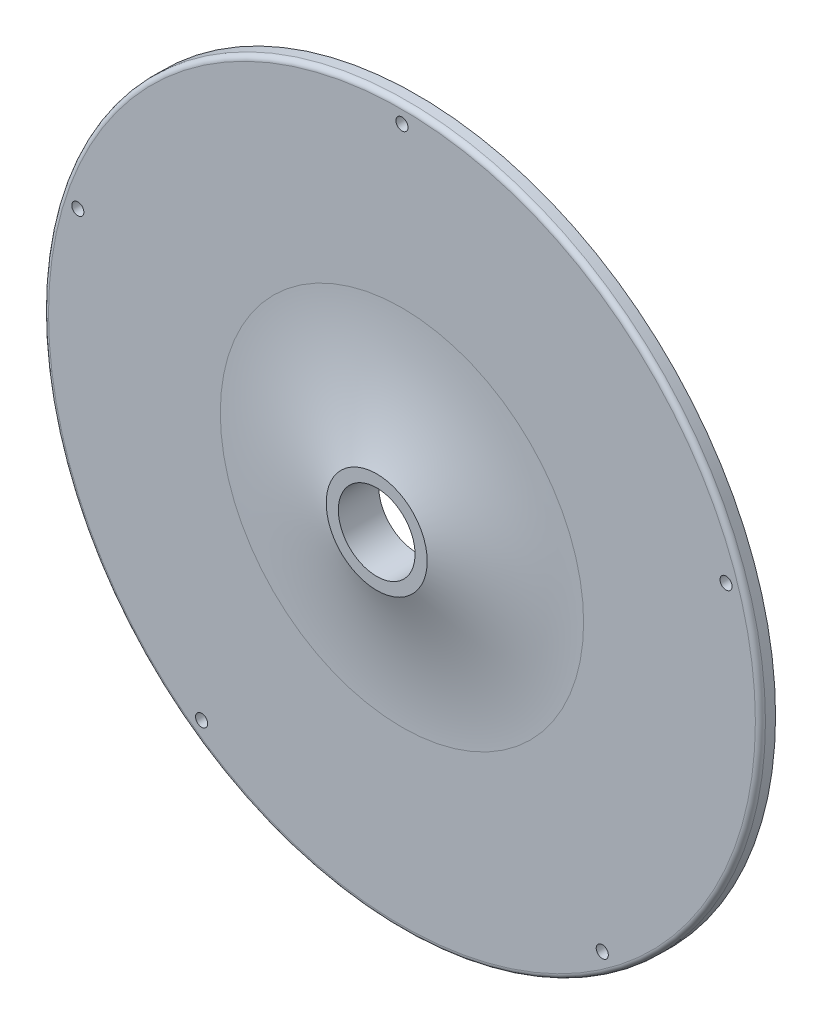
SolidWorks part; units mm, degrees
ref_plane "Front Plane" through (0, 0, 0) normal (0, 0, 1) x (1, 0, 0)
ref_plane "Top Plane" through (0, 0, 0) normal (0, 1, 0) x (1, 0, 0)
ref_plane "Right Plane" through (0, 0, 0) normal (1, 0, 0) x (0, 0, -1)
ref_axis "X AXIS" through (-88.99, 0, 0) along (1, 0, 0)
ref_axis "Y AXIS" through (0, 55, 0) along (0, -1, 0)
ref_axis "Z AXIS" through (0, 0, -88.99) along (0, 0, 1)
sketch "Sketch2" plane through (0, 0, 0) normal (0, 0, 1) x (1, 0, 0)
  circle A0 centre (0, 0) radius 81.28
  dimension "D1" = 162.56
extrude "Boss-Extrude1" add sketch "Sketch2" against normal blind 1.27
sketch "Sketch3" plane through (0, 0, 0) normal (0, 0, 1) x (1, 0, 0)
  circle A0 centre (0, 0) radius 90.17
  dimension "D1" = 180.34
extrude "Boss-Extrude2" add sketch "Sketch3" along normal blind 3.81
sketch "Sketch4" plane through (0, 0, 0) normal (0, 0, 1) x (1, 0, 0)
  line L0 (0, 88.9) -> (0, 82.55) construction
  circle A0 centre (0, 0) radius 82.55 construction
  circle A1 centre (0, 0) radius 88.9 construction
  circle A2 centre (0, 85.725) radius 1.524
  dimension "D1" = 165.1
  dimension "D2" = 177.8
  dimension "D3" = 3.048
extrude "Cut-Extrude2" cut sketch "Sketch4" along normal through all
pattern_circular "CirPattern1" count 5 over 360 about axis through (0, 0, 3.81) along (0, 0, 1) of "Cut-Extrude2"
sketch "Sketch14" plane through (0, 0, 3.81) normal (0, 0, 1) x (1, 0, 0)
  circle A0 centre (0, 0) radius 6.477
  circle A1 centre (0, 0) radius 12.7
  dimension "D1" = 12.954
  dimension "D2" = 25.4
extrude "Boss-Extrude3" add sketch "Sketch14" along normal blind 6.35 contours A1 A0 region at (-12.3408, 0, 3.81)
sketch "Sketch23" plane through (0, 0, -1.27) normal (0, 0, -1) x (-1, 0, 0)
  circle A0 centre (0, 0) radius 13.97
  dimension "D1" = 27.94
extrude "Cut-Extrude3" cut sketch "Sketch23" against normal blind 1.27
sketch "Sketch24" plane through (0, 0, 0) normal (0, 0, -1) x (-1, 0, 0)
  circle A0 centre (0, 0) radius 9.652
  dimension "D1" = 19.304
extrude "Cut-Extrude4" cut sketch "Sketch24" against normal through all
fillet "Fillet1" radius 88.9 1 edges at (12.7, 0, 3.81)
fillet "Fillet2" radius 1.27 1 edges at (90.17, 0, 3.81)
